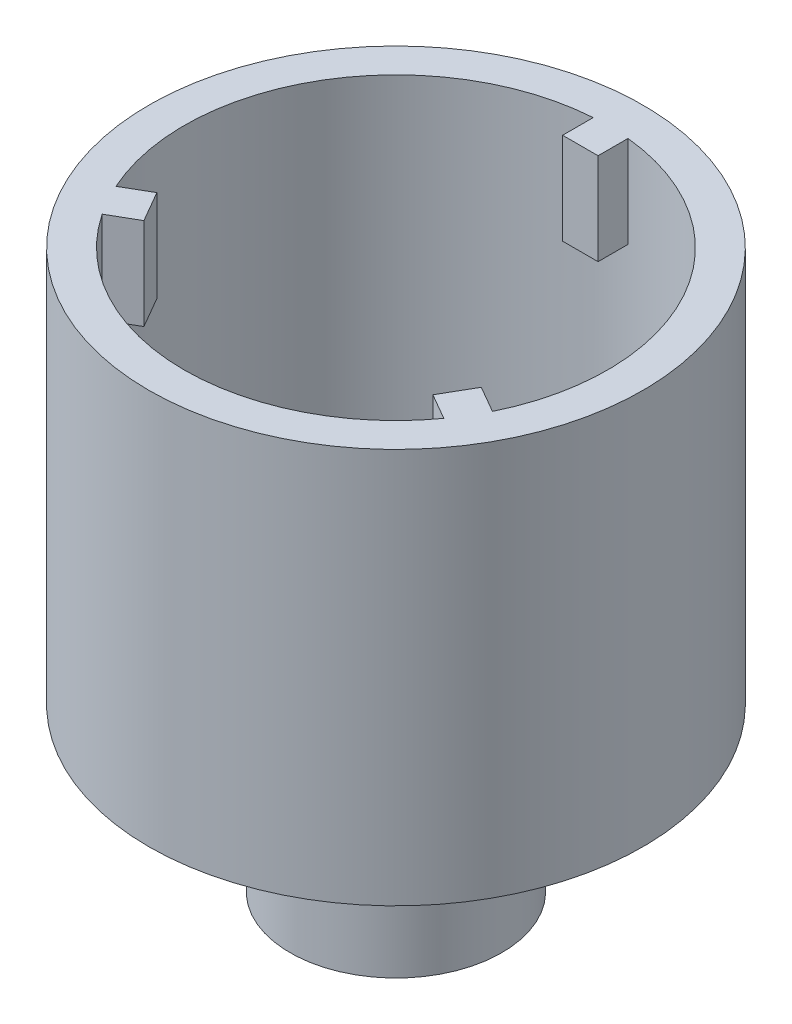
SolidWorks part; units mm, degrees
ref_plane "Front Plane" through (0, 0, 0) normal (0, 0, 1) x (1, 0, 0)
ref_plane "Top Plane" through (0, 0, 0) normal (0, 1, 0) x (1, 0, 0)
ref_plane "Right Plane" through (0, 0, 0) normal (1, 0, 0) x (0, 0, -1)
sketch "Sketch1" plane through (0, 0, 0) normal (0, 1, 0) x (1, 0, 0)
  circle A0 centre (0, 0) radius 35
  dimension "D1" = 70
extrude "Boss-Extrude1" add sketch "Sketch1" along normal blind 56
sketch "Sketch2" plane through (0, 56, 0) normal (0, 1, 0) x (1, 0, 0)
  circle A0 centre (0, 0) radius 30
  dimension "D1" = 60
extrude "Cut-Extrude1" cut sketch "Sketch2" against normal blind 46.9
sketch "Sketch3" plane through (0, 0, 0) normal (0, -1, 0) x (1, 0, 0)
  circle A0 centre (0, 0) radius 19.5
  dimension "D1" = 39
extrude "Boss-Extrude2" add sketch "Sketch3" along normal blind 7
sketch "Sketch4" plane through (0, -7, 0) normal (0, -1, 0) x (1, 0, 0)
  circle A0 centre (0, 0) radius 15
  dimension "D1" = 30
extrude "Boss-Extrude3" add sketch "Sketch4" along normal blind 16
fillet "Fillet1" radius 5 1 edges at (0, 0, -19.5)
sketch "Sketch5" plane through (0, 56, 0) normal (0, 1, 0) x (1, 0, 0)
  line L0 (-1.9905, 29.9339) -> (-1.9905, 25.6053)
  line L1 (-1.9905, 25.6053) -> (3.0302, 25.6053)
  line L2 (3.0302, 25.6053) -> (3.0302, 29.8466)
  line L3 (26.9188, -13.2431) -> (23.1701, -11.0788)
  line L4 (23.1701, -11.0788) -> (20.6597, -15.4269)
  line L5 (20.6597, -15.4269) -> (24.3328, -17.5475)
  line L6 (-24.9282, -16.6908) -> (-21.1796, -14.5265)
  line L7 (-21.1796, -14.5265) -> (-23.69, -10.1784)
  line L8 (-23.69, -10.1784) -> (-27.363, -12.299)
  circle A0 centre (0, 0) radius 30 construction
  arc A1 (24.3328, -17.5475) -> (26.9188, -13.2431) centre (0, 0) ccw
  circle A2 centre (0, 0) radius 30
  arc A3 (3.0302, 29.8466) -> (-1.9905, 29.9339) centre (0, 0) ccw
  arc A4 (-27.363, -12.299) -> (-24.9282, -16.6908) centre (0, 0) ccw
  point P19 (0, 0)
  dimension "D1" = 0
  dimension "D2" = 3
extrude "Boss-Extrude4" add sketch "Sketch5" against normal blind 13
